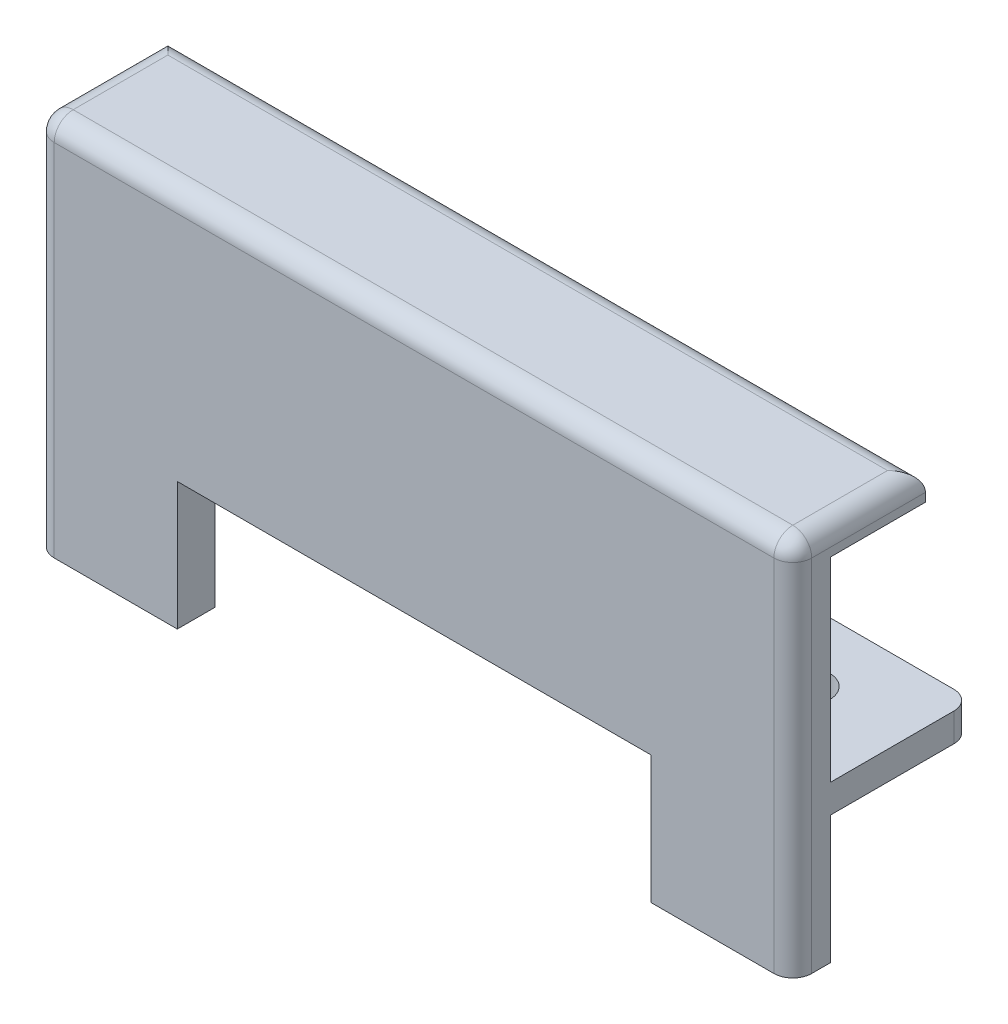
SolidWorks part; units mm, degrees
ref_plane "前视基准面" through (0, 0, 0) normal (0, 0, 1) x (1, 0, 0)
ref_plane "上视基准面" through (0, 0, 0) normal (0, 1, 0) x (1, 0, 0)
ref_plane "右视基准面" through (0, 0, 0) normal (1, 0, 0) x (0, 0, -1)
sketch "草图1" plane through (0, 0, 0) normal (0, 0, 1) x (1, 0, 0)
  line L0 (0, -1000) -> (0, 49000) construction
  line L1 (-3.2, 10) -> (-3.2, 8.5) construction
  line L2 (-10, -10) -> (10, -10) construction
  line L3 (-10, -10) -> (-10, 10) construction
  line L4 (-10, 10) -> (10, 10) construction
  line L5 (-1000, 0) -> (49000, 0) construction
  line L6 (10, -10) -> (10, 10) construction
  line L7 (-10, -10) -> (10, 10) construction
  line L8 (-10, 10) -> (10, -10) construction
  line L9 (-3.2, 8.5) -> (-5.5, 8.5) construction
  line L10 (-5.5, 8.5) -> (-5.5, 6.7) construction
  line L11 (-5.5, 6.7) -> (-2.8, 4) construction
  line L12 (-2.8, 4) -> (2.8, 4) construction
  line L13 (5.5, 6.7) -> (2.8, 4) construction
  line L14 (5.5, 8.5) -> (5.5, 6.7) construction
  line L15 (3.2, 8.5) -> (5.5, 8.5) construction
  line L16 (3.2, 10) -> (3.2, 8.5) construction
  line L17 (8.5, 3.2) -> (8.5, 5.5) construction
  line L18 (8.5, 5.5) -> (6.7, 5.5) construction
  line L19 (6.7, 5.5) -> (4, 2.8) construction
  line L20 (4, 2.8) -> (4, -2.8) construction
  line L21 (6.7, -5.5) -> (4, -2.8) construction
  line L22 (8.5, -5.5) -> (6.7, -5.5) construction
  line L23 (8.5, -3.2) -> (8.5, -5.5) construction
  line L24 (10, 3.2) -> (8.5, 3.2) construction
  line L25 (10, -3.2) -> (8.5, -3.2) construction
  line L26 (3.2, -8.5) -> (5.5, -8.5) construction
  line L27 (5.5, -8.5) -> (5.5, -6.7) construction
  line L28 (5.5, -6.7) -> (2.8, -4) construction
  line L29 (2.8, -4) -> (-2.8, -4) construction
  line L30 (-5.5, -6.7) -> (-2.8, -4) construction
  line L31 (-5.5, -8.5) -> (-5.5, -6.7) construction
  line L32 (-3.2, -8.5) -> (-5.5, -8.5) construction
  line L33 (3.2, -10) -> (3.2, -8.5) construction
  line L34 (-3.2, -10) -> (-3.2, -8.5) construction
  line L35 (-8.5, -3.2) -> (-8.5, -5.5) construction
  line L36 (-8.5, -5.5) -> (-6.7, -5.5) construction
  line L37 (-6.7, -5.5) -> (-4, -2.8) construction
  line L38 (-4, -2.8) -> (-4, 2.8) construction
  line L39 (-6.7, 5.5) -> (-4, 2.8) construction
  line L40 (-8.5, 5.5) -> (-6.7, 5.5) construction
  line L41 (-8.5, 3.2) -> (-8.5, 5.5) construction
  line L42 (-10, -3.2) -> (-8.5, -3.2) construction
  line L43 (-10, 3.2) -> (-8.5, 3.2) construction
  line L44 (-10, 10) -> (-50, 10) construction
  line L45 (-50, 10) -> (-50, -10) construction
  line L46 (-50, -10) -> (-10, -10) construction
  line L47 (-50, -10) -> (21, -10)
  line L48 (-21, 30) -> (21, 30) construction
  line L49 (-21, 30) -> (-21, 44.755)
  line L50 (-16, 72) -> (-6.245, 72)
  line L51 (21, 30) -> (21, 44.755)
  line L52 (-21, 30) -> (21, 72) construction
  line L53 (-21, 72) -> (21, 30) construction
  line L54 (-50, 10) -> (-70, 10)
  line L55 (-50, -10) -> (-70, -10)
  line L56 (-50, -10) -> (-50, 13)
  line L57 (-50, 13) -> (-70, 13)
  line L58 (21, -10) -> (21, 30)
  line L59 (-21, 13) -> (-50, 13)
  line L60 (-50, 10) -> (10, 10)
  line L61 (-21, 13) -> (-21, 30)
  line L62 (6.245, 72) -> (16, 72)
  line L63 (-21, 57.245) -> (-21, 67)
  line L64 (21, 57.245) -> (21, 67)
  line L65 (-21, 13) -> (10, 13)
  line L66 (10, 13) -> (10, 10)
  line L67 (-50, -10) -> (-50, 10) construction
  line L68 (-24.55, 6) -> (-15.45, 6)
  line L69 (-50, 13) -> (-50, 10) construction
  line L70 (-3.05, 10) -> (-3.05, 8)
  line L71 (-3.05, 8) -> (-5.05, 8)
  line L72 (-5.05, 8) -> (-5.05, 6.5)
  line L73 (-5.05, 6.5) -> (-4.55, 6)
  line L74 (-4.55, 6) -> (4.55, 6)
  line L75 (5.05, 6.5) -> (4.55, 6)
  line L76 (5.05, 8) -> (5.05, 6.5)
  line L77 (3.05, 10) -> (3.05, 8)
  line L78 (3.05, 8) -> (5.05, 8)
  line L79 (-14.95, 6.5) -> (-15.45, 6)
  line L80 (-14.95, 8) -> (-14.95, 6.5)
  line L81 (-16.95, 8) -> (-14.95, 8)
  line L82 (-16.95, 10) -> (-16.95, 8)
  line L83 (-23.05, 10) -> (-23.05, 8)
  line L84 (-23.05, 8) -> (-25.05, 8)
  line L85 (-25.05, 8) -> (-25.05, 6.5)
  line L86 (-25.05, 6.5) -> (-24.55, 6)
  line L87 (-44.55, 6) -> (-35.45, 6)
  line L88 (-34.95, 6.5) -> (-35.45, 6)
  line L89 (-34.95, 8) -> (-34.95, 6.5)
  line L90 (-36.95, 8) -> (-34.95, 8)
  line L91 (-36.95, 10) -> (-36.95, 8)
  line L92 (-43.05, 10) -> (-43.05, 8)
  line L93 (-43.05, 8) -> (-45.05, 8)
  line L94 (-45.05, 8) -> (-45.05, 6.5)
  line L95 (-45.05, 6.5) -> (-44.55, 6)
  line L96 (-30, 10) -> (-30, -10) construction
  line L97 (-40, 10) -> (-40, -10) construction
  line L98 (-34, 4.55) -> (-34, -4.55)
  line L99 (-33.5, -5.05) -> (-34, -4.55)
  line L100 (-32, -5.05) -> (-33.5, -5.05)
  line L101 (-32, -3.05) -> (-32, -5.05)
  line L102 (-32, 3.05) -> (-28, 3.05)
  line L103 (-28, -3.05) -> (-32, -3.05)
  line L104 (-32, 3.05) -> (-32, 5.05)
  line L105 (-32, 5.05) -> (-33.5, 5.05)
  line L106 (-33.5, 5.05) -> (-34, 4.55)
  line L107 (-35.45, -6) -> (-44.55, -6)
  line L108 (-45.05, -6.5) -> (-44.55, -6)
  line L109 (-45.05, -8) -> (-45.05, -6.5)
  line L110 (-43.05, -8) -> (-45.05, -8)
  line L111 (-43.05, -10) -> (-43.05, -8)
  line L112 (-36.95, -10) -> (-36.95, -8)
  line L113 (-36.95, -8) -> (-34.95, -8)
  line L114 (-34.95, -8) -> (-34.95, -6.5)
  line L115 (-34.95, -6.5) -> (-35.45, -6)
  line L116 (-46, -4.55) -> (-46, 4.55) construction
  line L117 (-46.5, 5.05) -> (-46, 4.55) construction
  line L118 (-48, 5.05) -> (-46.5, 5.05) construction
  line L119 (-48, 3.05) -> (-48, 5.05) construction
  line L120 (-50, 3.05) -> (-48, 3.05) construction
  line L121 (-50, -3.05) -> (-48, -3.05) construction
  line L122 (-48, -3.05) -> (-48, -5.05) construction
  line L123 (-48, -5.05) -> (-46.5, -5.05) construction
  line L124 (-46.5, -5.05) -> (-46, -4.55) construction
  line L125 (-26.5, 5.05) -> (-26, 4.55)
  line L126 (-28, 5.05) -> (-26.5, 5.05)
  line L127 (-28, 3.05) -> (-28, 5.05)
  line L128 (-28, -3.05) -> (-28, -5.05)
  line L129 (-28, -5.05) -> (-26.5, -5.05)
  line L130 (-26.5, -5.05) -> (-26, -4.55)
  line L131 (-26, 4.55) -> (-26, -4.55)
  line L132 (-30, -3.05) -> (-32, -3.05) [skipped]
  line L133 (-30, 3.05) -> (-32, 3.05) [skipped]
  line L134 (-25.05, -6.5) -> (-24.55, -6)
  line L135 (-25.05, -8) -> (-25.05, -6.5)
  line L136 (-23.05, -8) -> (-25.05, -8)
  line L137 (-23.05, -10) -> (-23.05, -8)
  line L138 (-16.95, -10) -> (-16.95, -8)
  line L139 (-16.95, -8) -> (-14.95, -8)
  line L140 (-14.95, -8) -> (-14.95, -6.5)
  line L141 (-14.95, -6.5) -> (-15.45, -6)
  line L142 (-24.55, -6) -> (-15.45, -6)
  line L143 (-70, -10) -> (-70, 13)
  circle A0 centre (0, 51) radius 11.5
  circle A1 centre (15.5, 66.5) radius 1.7
  circle A2 centre (15.5, 35.5) radius 1.7
  circle A3 centre (-15.5, 35.5) radius 1.7
  circle A4 centre (-15.5, 66.5) radius 1.7
  arc A5 (16, 72) -> (21, 67) centre (16, 67) cw
  arc A6 (-21, 67) -> (-16, 72) centre (-16, 67) cw
  arc A7 (-2.3419, 70.125) -> (2.3419, 70.125) centre (0, 72) ccw
  arc A8 (-2.3419, 70.125) -> (-6.245, 72) centre (-6.245, 67) ccw
  arc A9 (2.3419, 70.125) -> (6.245, 72) centre (6.245, 67) cw
  arc A10 (19.125, 53.3419) -> (19.125, 48.6581) centre (21, 51) ccw
  arc A11 (19.125, 48.6581) -> (21, 44.755) centre (16, 44.755) cw
  arc A12 (19.125, 53.3419) -> (21, 57.245) centre (16, 57.245) ccw
  arc A16 (-19.125, 48.6581) -> (-19.125, 53.3419) centre (-21, 51) ccw
  arc A17 (-19.125, 53.3419) -> (-21, 57.245) centre (-16, 57.245) cw
  arc A18 (-19.125, 48.6581) -> (-21, 44.755) centre (-16, 44.755) ccw
  point P0 (0, 0)
  point P18 (0, 4)
  point P23 (0, 51)
  point P58 (0, 0)
  point P82 (0, 51)
  point P93 (3, 72)
  point P110 (0, 6)
  point P118 (0, 51)
  point P154 (-40, 0)
  point P176 (-40, 0)
  point P188 (-40, 0)
  dimension "D12" = 3
  dimension "D17" = 3.4
  dimension "D20" = 5
  dimension "D21" = 3
  dimension "D22" = 5
  dimension "D23" = 5
  dimension "D1" = 20
  dimension "D2" = 20
  dimension "D3" = 6.4
  dimension "D4" = 1.5
  dimension "D5" = 11
  dimension "D6" = 6
  dimension "D7" = 1.8
  dimension "D9" = 60
  dimension "D10" = 42
  dimension "D11" = 42
  dimension "D13" = 20
  dimension "D14" = 41
  dimension "D15" = 20
  dimension "D16" = 3
  dimension "D19" = 31
  dimension "D26" = 3.05
  dimension "D27" = 2
  dimension "D28" = 2
  dimension "D29" = 1.5
  dimension "D30" = 2
  dimension "D31" = 4.55
  dimension "D33" = 10
  dimension "D8" = 10
  dimension "D18" = 4
extrude "凸台-拉伸1" add sketch "草图1" along normal blind 4 contours L66 L65 | L78 L77 L60 L70 L71 L72 L73 L74 L75 L76 | L98 L105 L104 L60 | L107 | L136 L130 L47 L103 | L116 L123 L47 | L85 L86 L68 L79 L80 L81 L82 L60 L83 L84 | L94 L95 L87 L88 L89 L90 L91 L60 L92 L93 | L114 L115 L107 L108 L109 L110 L111 L47 L112 L113 | L131 L125 L126 L127 L102 L104 L105 L106 L98 L99 L100 L101 L103 L128 L129 L130 | L142 L134 L135 L136 L137 L47 L138 L139 L140 L141 | L143 L55 L56 L54 | L143 L54 L56 L57 | L59 L61 region at (-4.4762, 24.6567, 0) region at (-60, 0, 0) region at (-40, -7.7654, 0) region at (-60, 11.5, 0) region at (-20, 11.5, 0) region at (-40, 7.7654, 0) region at (-20, -7.7654, 0) region at (-20, 7.7654, 0) region at (0, 7.7654, 0) region at (-30, 0, 0)
extrude "凸台-拉伸2" add sketch "草图1<4>" against normal blind 10 contours L66 L65 | L143 L54 L56 L57 region at (-60, 11.5, 0) region at (-20, 11.5, 0)
sketch "草图1<4>" plane through (0, 0, 0) normal (0, 0, 1) x (1, 0, 0) same geometry as "草图1"
extrude "凸台-拉伸3" add sketch "草图1<5>" against normal blind 10 contours L78 L77 L60 L70 L71 L72 L73 L74 L75 L76 | L85 L86 L68 L79 L80 L81 L82 L60 L83 L84 | L94 L95 L87 L88 L89 L90 L91 L60 L92 L93 | L131 L125 L126 L127 L102 L104 L105 L106 L98 L99 L100 L101 L103 L128 L129 L130 | L142 L134 L135 L136 L137 L47 L138 L139 L140 L141 | L114 L115 L107 L108 L109 L110 L111 L47 L112 L113 region at (-40, -7.7654, 0) region at (-40, 7.7654, 0) region at (-20, -7.7654, 0) region at (-20, 7.7654, 0) region at (0, 7.7654, 0) region at (-30, 0, 0)
sketch "草图1<5>" plane through (0, 0, 0) normal (0, 0, 1) x (1, 0, 0) same geometry as "草图1"
sketch "草图4" plane through (10, 0, 0) normal (1, 0, 0) x (0, 0, -1)
  line L0 (10, 13) -> (0, 33)
  line L2 (0, 13) -> (0, 44.755) construction
  dimension "D2" = 10
rib "筋2" sketch "草图4" sketch "草图4" thickness 5 extrusion direction parallel to sketch draft on no parameters "D1"=5
mirror "镜向1" about plane through (0, 0, 0) normal (1, 0, 0) of "筋2"
sketch "草图5" plane through (0, 0, -10) normal (0, 0, -1) x (-1, 0, 0)
  line L0 (16.95, 10) -> (16.95, 8) construction
  line L1 (14.95, 8) -> (16.95, 8)
  line L2 (14.95, 8) -> (14.95, 7.9)
  line L3 (14.95, 7.9) -> (16.95, 7.9)
  line L4 (16.95, 8) -> (16.95, 7.9)
  line L5 (-1000, 0) -> (49000, 0) construction
  line L6 (30, -996.95) -> (30, 49003.05) construction
  line L7 (32, 3.05) -> (28, 3.05) construction
  line L8 (20, -993.9) -> (20, 49006.1) construction
  line L9 (24.55, 6) -> (15.45, 6) construction
  line L10 (40, -993.9) -> (40, 49006.1) construction
  line L11 (44.55, 6) -> (35.45, 6) construction
  line L12 (23.05, 8) -> (23.05, 7.9)
  line L13 (25.05, 7.9) -> (23.05, 7.9)
  line L14 (25.05, 8) -> (25.05, 7.9)
  line L15 (25.05, 8) -> (23.05, 8)
  line L16 (34.95, 8) -> (36.95, 8)
  line L17 (34.95, 8) -> (34.95, 7.9)
  line L18 (34.95, 7.9) -> (36.95, 7.9)
  line L19 (36.95, 8) -> (36.95, 7.9)
  line L20 (43.05, 8) -> (43.05, 7.9)
  line L21 (45.05, 7.9) -> (43.05, 7.9)
  line L22 (45.05, 8) -> (45.05, 7.9)
  line L23 (45.05, 8) -> (43.05, 8)
  line L24 (28, 5.05) -> (26.5, 5.05) construction
  line L25 (27.9, 5.05) -> (32.1, 5.05)
  line L26 (27.9, 5.05) -> (27.9, 3.05)
  line L27 (27.9, 3.05) -> (32.1, 3.05)
  line L28 (32.1, 5.05) -> (32.1, 3.05)
  line L29 (32, 3.05) -> (28, 3.05) construction
  line L30 (32, 3.05) -> (32, 5.05) construction
  line L31 (32.1, -5.05) -> (32.1, -3.05)
  line L32 (27.9, -3.05) -> (32.1, -3.05)
  line L33 (27.9, -5.05) -> (27.9, -3.05)
  line L34 (27.9, -5.05) -> (32.1, -5.05)
  line L35 (40, 993.9) -> (40, -49006.1) construction
  line L36 (20, 993.9) -> (20, -49006.1) construction
  line L37 (30, 996.95) -> (30, -49003.05) construction
  line L38 (45.05, -8) -> (43.05, -8)
  line L39 (45.05, -8) -> (45.05, -7.9)
  line L40 (45.05, -7.9) -> (43.05, -7.9)
  line L41 (43.05, -8) -> (43.05, -7.9)
  line L42 (36.95, -8) -> (36.95, -7.9)
  line L43 (34.95, -7.9) -> (36.95, -7.9)
  line L44 (34.95, -8) -> (34.95, -7.9)
  line L45 (34.95, -8) -> (36.95, -8)
  line L46 (25.05, -8) -> (23.05, -8)
  line L47 (25.05, -8) -> (25.05, -7.9)
  line L48 (25.05, -7.9) -> (23.05, -7.9)
  line L49 (23.05, -8) -> (23.05, -7.9)
  line L50 (16.95, -8) -> (16.95, -7.9)
  line L51 (14.95, -7.9) -> (16.95, -7.9)
  line L52 (14.95, -8) -> (14.95, -7.9)
  line L53 (14.95, -8) -> (16.95, -8)
  point P15 (30, 3.05)
  point P20 (20, 6)
  point P25 (40, 6)
  dimension "D1" = 0.1
  dimension "D2" = 0.1
extrude "切除-拉伸2" cut sketch "草图5" against normal up to surface (10 mm away) up to face at (-17.7096, 15.477, 0)
chamfer "倒角1" distance 0.25 angle 45 28 edges at (-32.1, -3.05, -5) (-32.1, -5.05, -5) (-27.9, -3.05, -5) (-27.9, -5.05, -5) (-32.1, 5.05, -5) (-32.1, 3.05, -5) (-27.9, 5.05, -5) (-27.9, 3.05, -5) (-5.05, 8, -5) (-3.05, 8, -5) (5.05, 8, -5) (3.05, 8, -5) (-45.05, 7.9, -5) (-43.05, 7.9, -5) (-25.05, 7.9, -5) (-23.05, 7.9, -5) (-34.95, 7.9, -5) (-36.95, 7.9, -5) (-14.95, 7.9, -5) (-16.95, 7.9, -5) (-25.05, -7.9, -5) (-23.05, -7.9, -5) (-45.05, -7.9, -5) (-43.05, -7.9, -5) (-34.95, -7.9, -5) (-36.95, -7.9, -5) (-16.95, -7.9, -5) (-14.95, -7.9, -5)
sketch "草图6" plane through (0, 0, 4) normal (0, 0, 1) x (1, 0, 0)
  line L0 (21, -10) -> (21, 44.755) construction
  line L1 (-70, -10) -> (21, -10)
  line L2 (-70, -10) -> (-70, -27)
  line L3 (-70, -27) -> (21, -27)
  line L4 (21, -10) -> (21, -27)
  line L5 (-70, -10) -> (-70, 13) construction
  line L6 (-21, 30) -> (21, 30) construction
  line L7 (-21, 30) -> (-21, 72) construction
  line L8 (-21, 72) -> (21, 72) construction
  line L9 (21, 30) -> (21, 72) construction
  line L10 (-21, 30) -> (21, 72) construction
  line L11 (-21, 72) -> (21, 30) construction
  point P7 (0, 51)
  dimension "D1" = 57
extrude "凸台-拉伸4" add sketch "草图6" against normal up to surface (4 mm away) up to face at (-18.9934, 12.645, 0)
sketch "草图7" plane through (0, 0, 0) normal (0, 0, -1) x (-1, 0, 0)
  line L1 (-10, -10) -> (70, -10)
  line L2 (-10, -10) -> (-10, -13.5)
  line L3 (-10, -13.5) -> (70, -13.5)
  line L4 (70, -10) -> (70, -13.5)
  line L5 (23.05, -10) -> (16.95, -10) construction
  line L6 (-10, 13) -> (-10, 10) construction
  line L7 (70, -27) -> (70, 10) construction
  dimension "D1" = 3.5
extrude "凸台-拉伸5" add sketch "草图7" along normal blind 15
sketch "草图8" plane through (0, 0, 0) normal (0, 0, -1) x (-1, 0, 0)
  line L0 (-10, -13.5) -> (70, -13.5) construction
  line L1 (55, -13.5) -> (5, -13.5)
  line L2 (55, -13.5) -> (55, -27)
  line L3 (55, -27) -> (5, -27)
  line L4 (5, -13.5) -> (5, -27)
  line L5 (-21, -27) -> (70, -27) construction
  line L6 (-16, 30) -> (21, 30) construction
  line L8 (70, -27) -> (70, -13.5) construction
  line L9 (21, 13) -> (21, 44.755) construction
  line L10 (-21, -27) -> (-10, -27)
  line L11 (-21, -27) -> (-21, 30)
  line L12 (-16, 30) -> (-14, 30)
  line L13 (-10, -27) -> (-10, 26)
  line L14 (16, 72) -> (6.245, 72) construction
  line L15 (-21, -27) -> (-21, 44.755) construction
  line L16 (-10, 33) -> (-10, 10) construction
  line L17 (-21, 35) -> (-21, 30)
  line L18 (-21, -27) -> (-21, 44.755) construction
  arc A0 (-21, 35) -> (-16, 30) centre (-16, 35) ccw
  arc A1 (-14, 30) -> (-10, 26) centre (-14, 26) cw
  point P20 (-10, 30)
  dimension "D4" = 10
  dimension "D5" = 4
  dimension "D1" = 15
  dimension "D2" = 15
  dimension "D3" = 42
extrude "切除-拉伸3" cut sketch "草图8" against normal through all
sketch "草图9" plane through (0, 0, -15) normal (0, 0, -1) x (-1, 0, 0)
  line L1 (50, -10) -> (25.4529, -10)
  line L2 (50, -10) -> (50, 5.5862)
  line L3 (50, 5.5862) -> (25.4529, 5.5862)
  line L4 (25.4529, 0.3648) -> (25.4529, 5.5862)
  line L5 (25.4529, 0.3648) -> (11.1226, 0.3648)
  line L6 (11.1226, 0.3648) -> (11.1226, -10)
  line L7 (16.95, -10) -> (-10, -10) construction
  line L8 (11.1226, -10) -> (25.4529, -10)
extrude "切除-拉伸4" cut sketch "草图9" against normal up to surface (15 mm away) up to face at (-30, 0, 0)
sketch "草图10" plane through (0, -13.5, 0) normal (0, -1, 0) x (1, 0, 0)
  line L0 (-30, 4) -> (-30, -15) construction
  line L1 (-5, 4) -> (-55, 4) construction
  line L2 (10, -15) -> (-70, -15) construction
  line L4 (10, -15) -> (10, 0) construction
  circle A0 centre (0, -7.5) radius 2.4
  circle A1 centre (-60, -7.5) radius 2.4
  dimension "D1" = 4.8
  dimension "D2" = 7.5
  dimension "D3" = 10
extrude "切除-拉伸5" cut sketch "草图10" against normal up to next
fillet "圆角1" radius 10 1 edges
sketch "草图11" plane through (0, 0, -15) normal (0, 0, -1) x (-1, 0, 0)
  line L0 (-10, 13) -> (-10, 10) construction
  line L1 (70, 13) -> (-22.1573, 13)
  line L2 (70, 13) -> (70, 72.8625)
  line L3 (70, 72.8625) -> (-22.1573, 72.8625)
  line L4 (-22.1573, 13) -> (-22.1573, 72.8625)
  line L5 (-10, 10.1) -> (70, 10.1)
  line L6 (-10, 10.1) -> (-10, -10.5)
  line L7 (-10, -10.5) -> (70, -10.5)
  line L8 (70, 10.1) -> (70, -10.5)
  line L10 (70, -10) -> (-10, -10) construction
  line L11 (70, -13.5) -> (70, -10) construction
  line L12 (70, 10) -> (43.05, 10) construction
  line M99 (-10, -10) -> (-10, -13.5)
  line M101 (70, -13.5) -> (70, -10)
  line M102 (70, -10) -> (-10, -10)
  dimension "D1" = 0.5
  dimension "D2" = 0.1
  dimension "D3" = 20.6
extrude "切除-拉伸6" cut sketch "草图11" against normal through all contours L4 L1 L2 L3 region at (-23.9213, 42.9313, -15)
extrude "切除-拉伸7" cut sketch "草图11<3>" against normal up to surface (15 mm away) contours L8 L5 L6 | L7 M99 M101 M102 region at (-30, 0.05, -15) region at (-30, -10.25, -15) up to face at (-22.4098, 6.8565, 0)
sketch "草图11<3>" plane through (0, 0, -15) normal (0, 0, -1) x (-1, 0, 0) same geometry as "草图11"
fillet "圆角2" radius 2 8 edges at (-30, 13, -10) (-70, 13, -3) (10, 13, -3) (-70, -7, 4) (10, -7, 4) (-30, 13, 4) (-70, -12, -15) (10, -12, -15)
